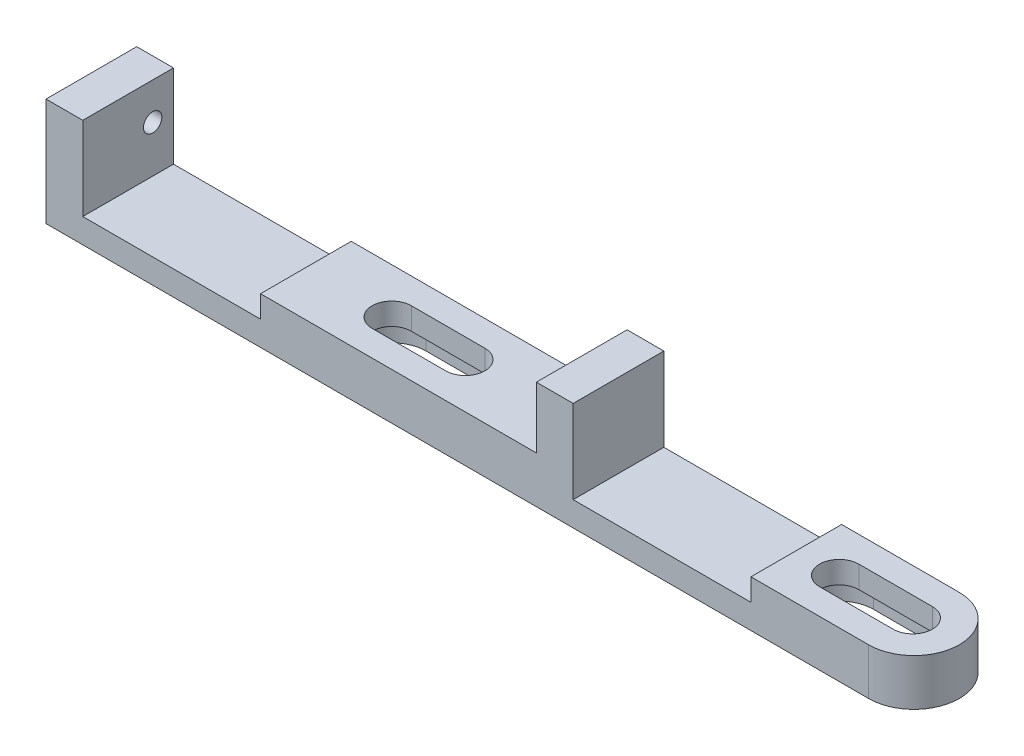
SolidWorks part; units mm, degrees
material "6061 Alloy"
ref_plane "Front Plane" through (0, 0, 0) normal (0, 0, 1) x (1, 0, 0)
ref_plane "Top Plane" through (0, 0, 0) normal (0, 1, 0) x (1, 0, 0)
ref_plane "Right Plane" through (0, 0, 0) normal (1, 0, 0) x (0, 0, -1)
sketch "Sketch1" plane through (0, 0, 0) normal (0, 0, 1) x (1, 0, 0)
  line L0 (0, 0) -> (0, 8.8)
  line L1 (0, 0) -> (70.8, 0)
  line L8 (70.8, 0) -> (70.8, 3.8)
  line L10 (0, 8.8) -> (3, 8.8)
  line L11 (3, 8.8) -> (3, 2)
  line L20 (40, 3.8) -> (40, 8.8)
  line L21 (40, 8.8) -> (43, 8.8)
  line L22 (43, 8.8) -> (43, 2)
  line L23 (40, 3.8) -> (17.5, 3.8)
  line L24 (17.5, 3.8) -> (17.5, 2)
  line L25 (17.5, 2) -> (3, 2)
  line L26 (70.8, 3.8) -> (57.5, 3.8)
  line L27 (57.5, 3.8) -> (57.5, 2)
  line L28 (57.5, 2) -> (43, 2)
  dimension "D1" = 3
  dimension "D2" = 2
  dimension "D3" = 8.8
  dimension "D4" = 3.8
  dimension "D5" = 14.5
  dimension "D6" = 3
  dimension "D7" = 40
  dimension "D8" = 14.5
  dimension "D10" = 70.8
extrude "Boss-Extrude1" add sketch "Sketch1" along normal blind 7.4
sketch "Sketch3" plane through (0, 3.8, 0) normal (0, 1, 0) x (1, 0, 0)
  line L0 (30.5, -3.7) -> (24.5, -3.7) construction
  line L1 (30.5, -5.3) -> (24.5, -5.3)
  line L2 (30.5, -2.1) -> (24.5, -2.1)
  line L3 (67, -3.7) -> (61, -3.7) construction
  line L4 (67, -5.3) -> (61, -5.3)
  line L5 (67, -2.1) -> (61, -2.1)
  line L6 (40, -7.4) -> (40, 0) construction
  arc A0 (30.5, -5.3) -> (30.5, -2.1) centre (30.5, -3.7) ccw
  arc A1 (24.5, -2.1) -> (24.5, -5.3) centre (24.5, -3.7) ccw
  arc A2 (67, -5.3) -> (67, -2.1) centre (67, -3.7) ccw
  arc A3 (61, -2.1) -> (61, -5.3) centre (61, -3.7) ccw
  point P2 (27.5, -3.7)
  point P7 (64, -3.7)
  point P21 (40, -3.7)
  dimension "D2" = 1.6
  dimension "D1" = 6
  dimension "D3" = 12.5
  dimension "D4" = 36.5
extrude "Cut-Extrude1" cut sketch "Sketch3" against normal blind 10
sketch "Sketch4" plane through (0, 0, 0) normal (0, -1, 0) x (1, 0, 0)
  line L0 (24.5, 5.3) -> (30.5, 5.3) construction
  line L1 (30.5, 2.1) -> (24.5, 2.1) construction
  line L2 (24.5, 5.3) -> (30.5, 5.3)
  line L3 (30.5, 2.1) -> (24.5, 2.1)
  line L4 (61, 5.3) -> (67, 5.3) construction
  line L5 (67, 2.1) -> (61, 2.1) construction
  line L6 (61, 5.3) -> (67, 5.3)
  line L7 (67, 2.1) -> (61, 2.1)
  line L8 (24.5, 6.5) -> (30.5, 6.5)
  line L9 (30.5, 0.9) -> (24.5, 0.9)
  line L10 (61, 6.5) -> (67, 6.5)
  line L11 (67, 0.9) -> (61, 0.9)
  arc A0 (30.5, 2.1) -> (30.5, 5.3) centre (30.5, 3.7) ccw construction
  arc A1 (24.5, 5.3) -> (24.5, 2.1) centre (24.5, 3.7) ccw construction
  arc A2 (30.5, 2.1) -> (30.5, 5.3) centre (30.5, 3.7) ccw
  arc A3 (24.5, 5.3) -> (24.5, 2.1) centre (24.5, 3.7) ccw
  arc A4 (61, 5.3) -> (61, 2.1) centre (61, 3.7) ccw construction
  arc A5 (67, 2.1) -> (67, 5.3) centre (67, 3.7) ccw construction
  arc A6 (61, 5.3) -> (61, 2.1) centre (61, 3.7) ccw
  arc A7 (67, 2.1) -> (67, 5.3) centre (67, 3.7) ccw
  arc A8 (30.5, 0.9) -> (30.5, 6.5) centre (30.5, 3.7) ccw
  arc A9 (24.5, 6.5) -> (24.5, 0.9) centre (24.5, 3.7) ccw
  arc A10 (67, 0.9) -> (67, 6.5) centre (67, 3.7) ccw
  arc A11 (61, 6.5) -> (61, 0.9) centre (61, 3.7) ccw
  dimension "D1" = 1.2
  dimension "D2" = 1.2
extrude "Cut-Extrude2" cut sketch "Sketch4" against normal blind 2
sketch "Sketch5" plane through (0, 0, 0) normal (-1, 0, 0) x (0, 0, 1)
  line L0 (7.4, 8.8) -> (0, 8.8) construction
  line L2 (7.4, 8.8) -> (7.4, 0) construction
  circle A0 centre (1.7, 5.8) radius 0.75
  dimension "D1" = 1.5
  dimension "D2" = 3
  dimension "D3" = 5.7
extrude "Cut-Extrude3" cut sketch "Sketch5" against normal up to next
sketch "Sketch6" plane through (0, 0, 0) normal (0, -1, 0) x (1, 0, 0)
  line L0 (70.8, 0) -> (70.8, 7.4)
  line L1 (70.8, 7.4) -> (70.8, 0) construction
  line L2 (70.8, 7.4) -> (67.1, 7.4)
  line L3 (0, 7.4) -> (70.8, 7.4) construction
  line L4 (0, 0) -> (70.8, 0) construction
  line L5 (67.1, 0) -> (70.8, 0)
  arc A0 (67.1, 7.4) -> (67.1, 0) centre (67.1, 3.7) cw
  line M13 (0, 0) -> (70.8, 0)
  line M14 (70.8, 0) -> (70.8, 7.4)
  line M15 (70.8, 7.4) -> (0, 7.4)
extrude "Cut-Extrude4" cut sketch "Sketch6" against normal blind 10 contours A0 M14 M13 | A0 L0 M15 region at (69.9735, 0, 0.8265) region at (69.9735, 0, 6.5735)
